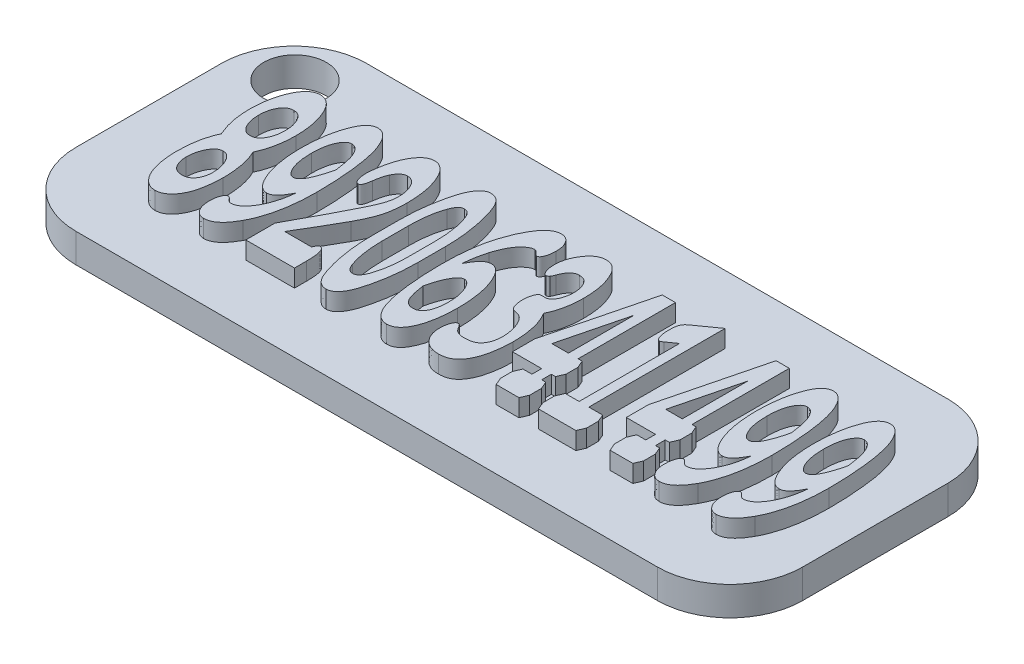
SolidWorks part; units mm, degrees
ref_plane "Спереди" through (0, 0, 0) normal (0, 0, 1) x (1, 0, 0)
ref_plane "Сверху" through (0, 0, 0) normal (0, 1, 0) x (1, 0, 0)
ref_plane "Справа" through (0, 0, 0) normal (1, 0, 0) x (0, 0, -1)
other "Configuration Table"
sketch "Эскиз1" plane through (0, 0, 0) normal (0, 1, 0) x (1, 0, 0)
  line L1 (0, 0) -> (50, 0)
  line L2 (0, 0) -> (0, 20)
  line L3 (0, 20) -> (50, 20)
  line L4 (50, 0) -> (50, 20)
  dimension "D1" = 20
  dimension "D2" = 50
extrude "Бобышка-Вытянуть1" add sketch "Эскиз1" along normal blind 2 contours L2 L3 L4 L1
sketch "Эскиз2" plane through (0, 2, 0) normal (0, 1, 0) x (1, 0, 0)
  line L0 (-2.8341, 4.1295) -> (51.2146, 4.1295) construction
  text T0 "<b> 89206341499</b>" font "Courier New" height in points 48
extrude "номер" add sketch "Эскиз2" along normal blind 1.2
fillet "Скругление1" radius 5 1 edges at (0, 1, -20)
fillet "Скругление2" radius 5 1 edges at (0, 1, 0)
fillet "Скругление3" radius 5 1 edges at (50, 1, -20)
fillet "Скругление4" radius 5 1 edges at (50, 1, 0)
sketch "Эскиз4" plane through (0, 2, 0) normal (0, 1, 0) x (1, 0, 0)
  circle A0 centre (3.5425, 16.5284) radius 2.1519
extrude "Вырез-Вытянуть1" cut sketch "Эскиз4" against normal blind 3
